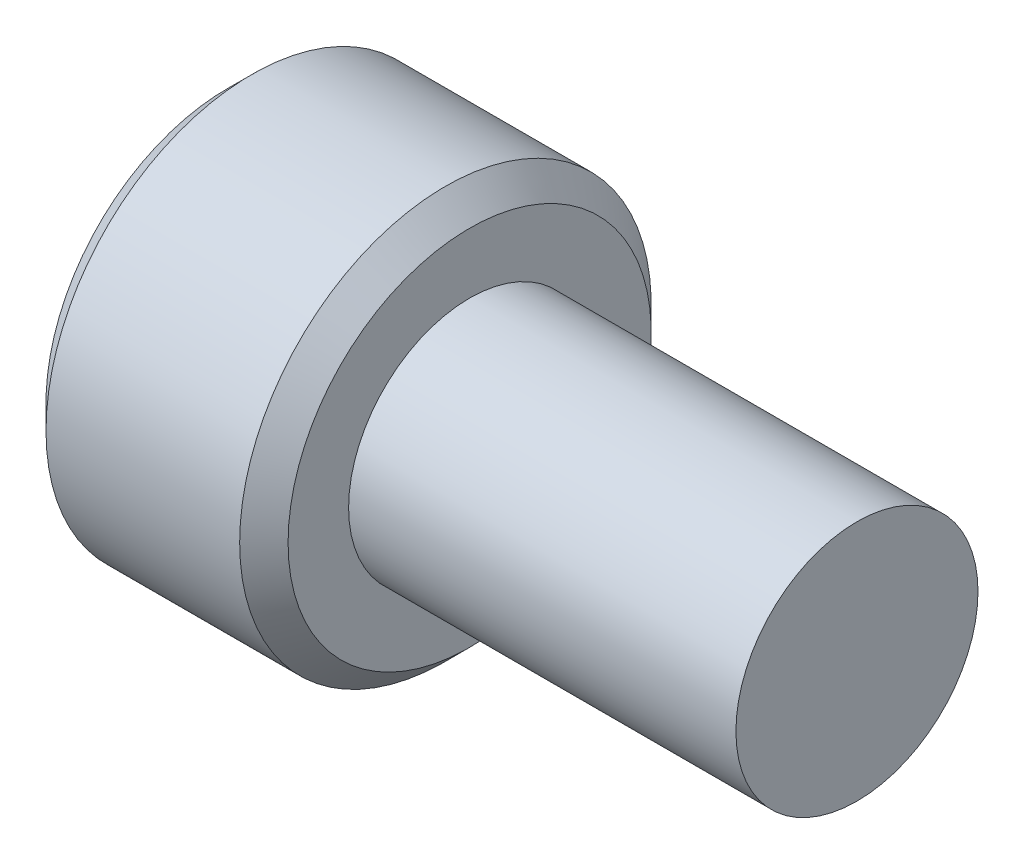
SolidWorks part; units mm, degrees
ref_plane "Front Plane" through (0, 0, 0) normal (0, 0, 1) x (1, 0, 0)
ref_plane "Top Plane" through (0, 0, 0) normal (0, 1, 0) x (1, 0, 0)
ref_plane "Right Plane" through (0, 0, 0) normal (1, 0, 0) x (0, 0, -1)
ref_axis "Axis_X" through (-5.65, 0, 0) along (1, 0, 0)
ref_axis "Axis_Y" through (0, 4.675, 0) along (0, -1, 0)
ref_axis "Axis_Z" through (0, 0, -4.675) along (0, 0, 1)
sketch "Sketch1" plane through (0, 0, 0) normal (0, 0, 1) x (1, 0, 0)
  line L0 (-5, 0) -> (8, 0) construction
  line L1 (0, 2.5) -> (8, 2.5)
  line L3 (-5, 0) -> (8, 0)
  line L4 (8, 2.5) -> (8, 0)
  line L6 (0, 2.5) -> (0, 4.25)
  line L7 (0, 4.25) -> (-5, 4.25)
  line L8 (-5, 0) -> (-5, 4.25)
  dimension "FIX_1" = 8
  dimension "FIX_3" = 5
  dimension "FIX_2" = 5
  dimension "FIX_4" = 8.5
revolve "Revolve1" add sketch "Sketch1" angle 360 about axis through (-5.65, 0, 0) along (1, 0, 0)
cosmetic thread "Thread1" parameters "FIX_7"=8, "FIX_6"=4.134
sketch "Sketch2" plane through (0, 0, 0) normal (0, 0, 1) x (1, 0, 0)
  line L0 (-1.7983, 0) -> (-3, 2)
  line L1 (-5, 0) -> (8, 0) construction
  line L2 (-3, 2) -> (-5, 2)
  line L3 (-5, 2) -> (-5, 0)
  line L4 (-5, 0) -> (-1.7983, 0) construction
  line L5 (-1.7983, 0) -> (-5, 0)
  dimension "FIX_8" = 59
  dimension "FIX_10" = 4
  dimension "FIX_9" = 2
revolve "Cut-Revolve1" cut sketch "Sketch2" angle 360 about axis through (-5.65, 0, 0) along (1, 0, 0)
sketch "Sketch3" plane through (-5, 0, 0) normal (-1, 0, 0) x (0, 0, 1)
  line L0 (0, -4.675) -> (0, 4.675) construction
  line L1 (2, 1.1547) -> (0, 2.3094)
  line L2 (0, 2.3094) -> (-2, 1.1547)
  line L3 (-2, 1.1547) -> (-2, -1.1547)
  line L4 (-2, -1.1547) -> (0, -2.3094)
  line L5 (0, -2.3094) -> (2, -1.1547)
  line L6 (2, -1.1547) -> (2, 1.1547)
  circle A0 centre (0, 0) radius 2 construction
  dimension "FIX_12" = 4
extrude "Cut-Extrude1" cut sketch "Sketch3" against normal blind 2
chamfer "Chamfer1" distance 0.5 angle 45 2 edges at (0, 0, 4.25) (-5, 0, 4.25)
equation "\"MSM_2\"=2"
equation "\"MSM_3\"=4.5"
equation "\"MSM_4\"=2.000000"
